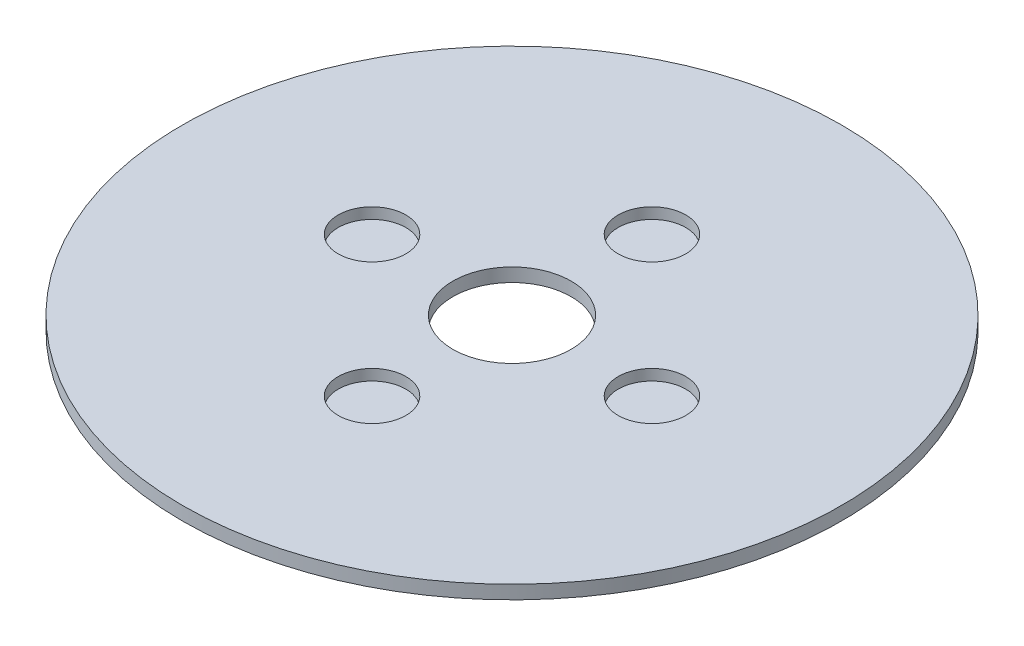
SolidWorks part; units mm, degrees
ref_plane "Front Plane" through (0, 0, 0) normal (0, 0, 1) x (1, 0, 0)
ref_plane "Top Plane" through (0, 0, 0) normal (0, 1, 0) x (1, 0, 0)
ref_plane "Right Plane" through (0, 0, 0) normal (1, 0, 0) x (0, 0, -1)
sketch "Sketch1" plane through (0, 0, 0) normal (0, 1, 0) x (1, 0, 0)
  circle A0 centre (0, 0) radius 97.5
  dimension "FLANGE_OD" = 195
extrude "Boss-Extrude1" add sketch "Sketch1" along normal blind 4
sketch "Sketch2" plane through (0, 0, 0) normal (0, 1, 0) x (1, 0, 0)
  circle A0 centre (0, 0) radius 17.5
  dimension "BORE_D" = 35
extrude "Cut-Extrude1" cut sketch "Sketch2" along normal through all
sketch "Sketch3" plane through (0, 4, 0) normal (0, 1, 0) x (1, 0, 0)
  circle A0 centre (0, 0) radius 41.4086 construction
  circle A1 centre (-41.4086, 0) radius 10
  dimension "BOLT_D" = 20
  dimension "BOLT_PCD" = 82.8171
extrude "Cut-Extrude2" cut sketch "Sketch3" against normal blind 3.2367
pattern_circular "CirPattern1" count 4 over 360 about axis through (0, 0, 0) along (0, 1, 0) of "Cut-Extrude2"
